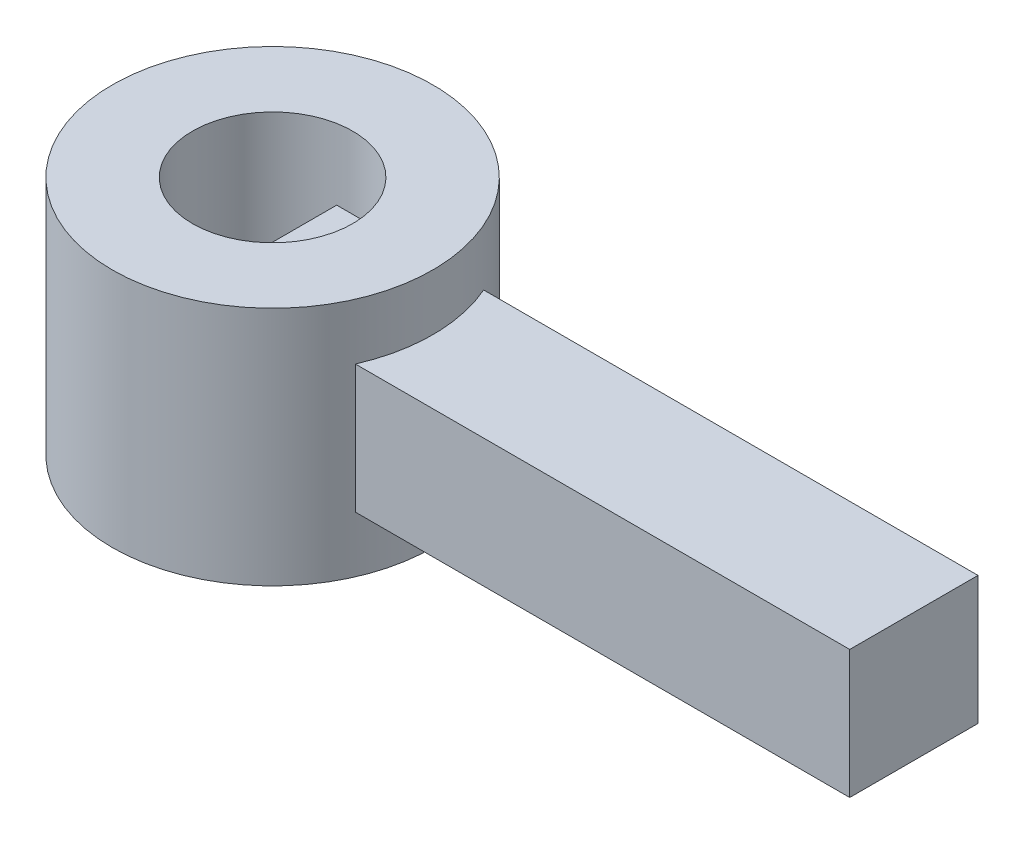
SolidWorks part; units mm, degrees
material "1023 Carbon Steel Sheet (SS)"
ref_plane "Front Plane" through (0, 0, 0) normal (0, 0, 1) x (1, 0, 0)
ref_plane "Top Plane" through (0, 0, 0) normal (0, 1, 0) x (1, 0, 0)
ref_plane "Right Plane" through (0, 0, 0) normal (1, 0, 0) x (0, 0, -1)
sketch "Sketch1" plane through (0, 0, 0) normal (0, 0, 1) x (1, 0, 0)
  line L0 (0, 5.715) -> (0, -5.715)
  arc A0 (0, -5.715) -> (0, 5.715) centre (0, 0) ccw
  dimension "D1" = 11.43
revolve "Revolve1" add sketch "Sketch1" angle 360 about L0
sketch "Sketch2" plane through (0, 0, 0) normal (0, 1, 0) x (1, 0, 0)
  circle A0 centre (0, 0) radius 3.175
  dimension "D1" = 6.35
extrude "Cut-Extrude1" cut sketch "Sketch2" against normal through all both and the other way through all
sketch "Sketch3" plane through (0, 0, 0) normal (0, 1, 0) x (1, 0, 0)
  circle A0 centre (0, 0) radius 3.175 construction
  circle A1 centre (0, 0) radius 3.175
  circle A2 centre (0, 0) radius 6.35
  dimension "D1" = 12.7
extrude "Boss-Extrude1" add sketch "Sketch3" along normal blind 4.7625 and the other way blind 4.7625
sketch "Sketch4" plane through (0, 0, 0) normal (1, 0, 0) x (0, 0, -1)
  line L1 (2.54, 2.54) -> (-2.54, 2.54)
  line L2 (2.54, 2.54) -> (2.54, -2.54)
  line L3 (2.54, -2.54) -> (-2.54, -2.54)
  line L4 (-2.54, 2.54) -> (-2.54, -2.54)
  line L5 (2.54, 2.54) -> (-2.54, -2.54) construction
  line L6 (2.54, -2.54) -> (-2.54, 2.54) construction
  point P0 (0, 0)
  dimension "D1" = 5.08
extrude "Boss-Extrude2" add sketch "Sketch4" along normal blind 25.4
